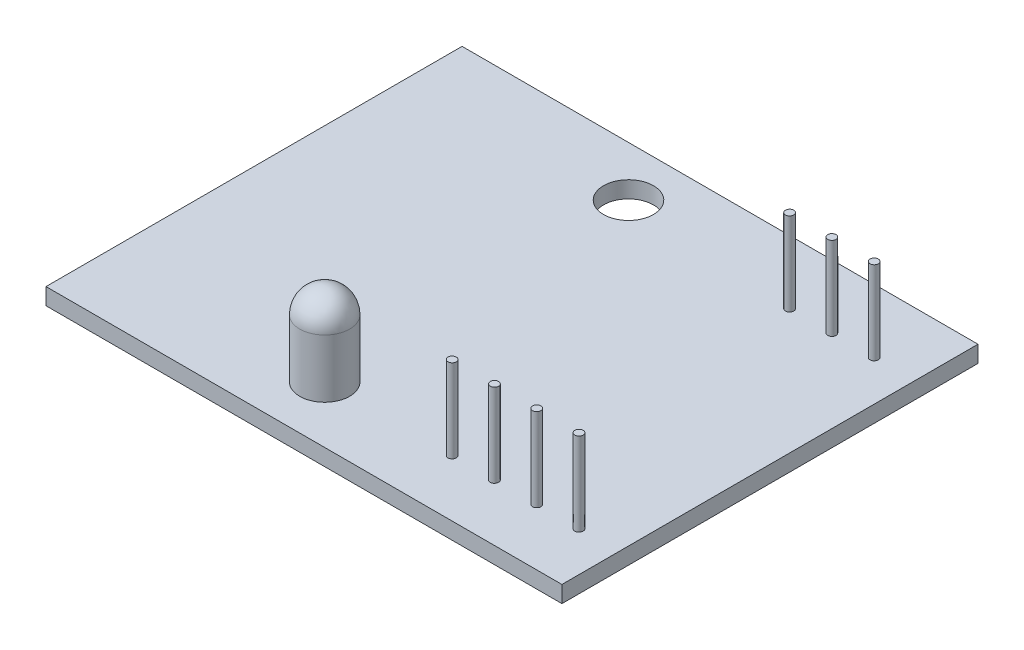
SolidWorks part; units mm, degrees
ref_plane "Přední rovina" through (0, 0, 0) normal (0, 0, 1) x (1, 0, 0)
ref_plane "Horní rovina" through (0, 0, 0) normal (0, 1, 0) x (1, 0, 0)
ref_plane "Pravá rovina" through (0, 0, 0) normal (1, 0, 0) x (0, 0, -1)
sketch "Skica1" plane through (0, 0, 0) normal (0, 1, 0) x (1, 0, 0)
  line L1 (0, 0) -> (31, 0)
  line L2 (0, 0) -> (0, 25)
  line L3 (0, 25) -> (31, 25)
  line L4 (31, 0) -> (31, 25)
  dimension "D1" = 25
  dimension "D2" = 31
extrude "Přidat vysunutím1" add sketch "Skica1" along normal blind 1
sketch "Skica2" plane through (0, 0, 0) normal (0, -1, 0) x (1, 0, 0)
  line L0 (1.5, -11.5) -> (1.5, -14.75)
  line L1 (1.5, -14.75) -> (2, -14.75)
  line L2 (2, -14.75) -> (2, -15.25)
  line L3 (2, -15.25) -> (1.5, -15.25)
  line L4 (1.5, -15.25) -> (1.5, -18.5)
  line L5 (1.5, -18.5) -> (8.5, -18.5)
  line L6 (8.5, -18.5) -> (8.5, -15.25)
  line L7 (8.5, -15.25) -> (8, -15.25)
  line L8 (8, -15.25) -> (8, -14.75)
  line L9 (8, -14.75) -> (8.5, -14.75)
  line L10 (8.5, -14.75) -> (8.5, -11.5)
  line L11 (8.5, -11.5) -> (1.5, -11.5)
  line L12 (0, -25) -> (0, 0) construction
  line L13 (1.5, -11.5) -> (8.5, -18.5) construction
  line L14 (31, -25) -> (0, -25) construction
  point P12 (5, -15)
  dimension "D1" = 7
  dimension "D2" = 7
  dimension "D3" = 0.5
  dimension "D4" = 5
  dimension "D5" = 10
extrude "Přidat vysunutím2" add sketch "Skica2" along normal blind 6 separate body
sketch "Skica3" plane through (0, -6, 0) normal (0, -1, 0) x (1, 0, 0)
  line L0 (1.5, -18.5) -> (8.5, -18.5) construction
  line L1 (1.5, -15.25) -> (1.5, -18.5) construction
  line L12 (8.5, -11.5) -> (1.5, -11.5) construction
  line L13 (2.5, -12.5) -> (7.5, -12.5)
  line L14 (2.5, -12.5) -> (2.5, -17.5)
  line L15 (2.5, -17.5) -> (7.5, -17.5)
  line L16 (7.5, -12.5) -> (7.5, -17.5)
  line L17 (8.5, -18.5) -> (8.5, -15.25) construction
  dimension "D1" = 1
  dimension "D2" = 1
  dimension "D3" = 1
  dimension "D4" = 1
extrude "Odebrat vysunutím1" cut sketch "Skica3" against normal blind 0.5
sketch "Skica4" plane through (0, 0, 0) normal (0, -1, 0) x (1, 0, 0)
  line L0 (0, -25) -> (0, 0) construction
  line L1 (31, -25) -> (0, -25) construction
  circle A0 centre (13, -22) radius 1.5
  dimension "D1" = 13
  dimension "D2" = 3
  dimension "D3" = 3
extrude "Odebrat vysunutím2" cut sketch "Skica4" against normal through all
chamfer "Zkosení1" distance 0.3 angle 45 6 edges at (8.5, -6, -16.875) (5, -6, -18.5) (1.5, -6, -16.875) (8.5, -6, -13.125) (5, -6, -11.5) (1.5, -6, -13.125)
sketch "Skica5" plane through (0, 1, 0) normal (0, 1, 0) x (1, 0, 0)
  line L0 (20.995, 3.41) -> (23.535, 3.41) construction
  line L1 (23.535, 3.41) -> (26.075, 3.41) construction
  line L3 (26.075, 3.41) -> (28.615, 3.41) construction
  line L4 (28.57, 21.19) -> (26.03, 21.19) construction
  line L5 (26.03, 21.19) -> (23.49, 21.19) construction
  line L6 (0, 25) -> (0, 0) construction
  line L7 (31, 25) -> (0, 25) construction
  circle A0 centre (20.995, 3.41) radius 0.25
  circle A1 centre (23.535, 3.41) radius 0.25
  circle A2 centre (26.075, 3.41) radius 0.25
  circle A3 centre (28.615, 3.41) radius 0.25
  circle A4 centre (28.57, 21.19) radius 0.25
  circle A5 centre (26.03, 21.19) radius 0.25
  circle A6 centre (23.49, 21.19) radius 0.25
  dimension "D2" = 0.5
  dimension "D4" = 3.81
  dimension "D5" = 20.995
  dimension "D6" = 21.59
  dimension "D1" = 2.54
  dimension "D3" = 28.57
extrude "Přidat vysunutím3" add sketch "Skica5" along normal blind 5 separate body
sketch "Skica7" plane through (0, 1, 0) normal (0, 1, 0) x (1, 0, 0)
  circle A0 centre (28.615, 3.41) radius 0.25 construction
  circle A1 centre (26.075, 3.41) radius 0.25 construction
  circle A2 centre (23.535, 3.41) radius 0.25 construction
  circle A3 centre (20.995, 3.41) radius 0.25 construction
  circle A4 centre (28.57, 21.19) radius 0.25 construction
  circle A5 centre (26.03, 21.19) radius 0.25 construction
  circle A6 centre (23.49, 21.19) radius 0.25 construction
  circle A21 centre (23.49, 21.19) radius 0.25
  circle A22 centre (26.03, 21.19) radius 0.25
  circle A23 centre (28.57, 21.19) radius 0.25
  circle A24 centre (20.995, 3.41) radius 0.25
  circle A25 centre (23.535, 3.41) radius 0.25
  circle A26 centre (26.075, 3.41) radius 0.25
  circle A27 centre (28.615, 3.41) radius 0.25
extrude "Přidat vysunutím5" add sketch "Skica7" along normal blind 0.5
sketch "Skica6" plane through (0, 1, 0) normal (0, 1, 0) x (1, 0, 0)
  line L0 (0, 25) -> (0, 0) construction
  line L1 (31, 25) -> (0, 25) construction
  circle A0 centre (13.335, 3.41) radius 1.5
  dimension "D1" = 13.335
  dimension "D2" = 21.59
  dimension "D3" = 3
extrude "Přidat vysunutím4" add sketch "Skica6" along normal blind 5
fillet "Zaoblit1" radius 1.5 1 edges at (13.335, 6, -1.91)
